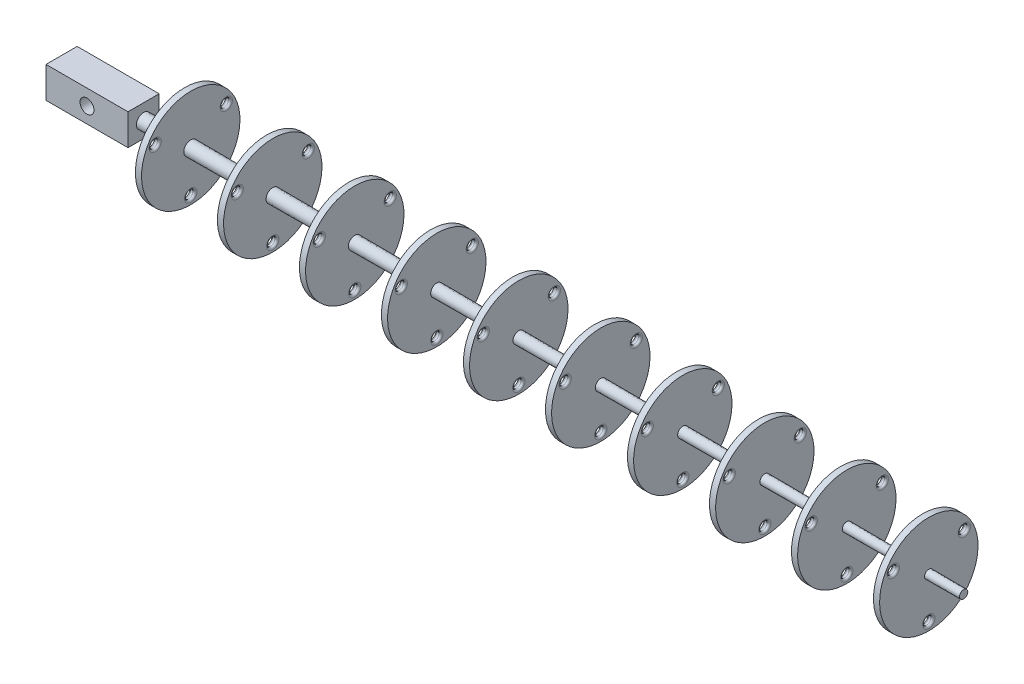
SolidWorks part; units mm, degrees
ref_plane "Front Plane" through (0, 0, 0) normal (0, 0, 1) x (1, 0, 0)
ref_plane "Top Plane" through (0, 0, 0) normal (0, 1, 0) x (1, 0, 0)
ref_plane "Right Plane" through (0, 0, 0) normal (1, 0, 0) x (0, 0, -1)
sketch "Sketch2" plane through (0, 0, 0) normal (0, 0, 1) x (1, 0, 0)
  line L0 (0, 1.75) -> (200, 1)
  line L1 (0, -11) -> (0, 11) construction
  line L2 (200, 1) -> (200, 0)
  line L3 (200, 0) -> (0, 0)
  line L4 (0, 0) -> (0, 1.75)
  dimension "D1" = 1.75
  dimension "D2" = 200
  dimension "D3" = 1
revolve "Revolve1" add sketch "Sketch2" angle 360 about L3
ref_axis "Axis1" through (-3.9062, 0, 0) along (1, 0, 0)
sketch "Sketch3" plane through (0, 0, 0) normal (0, 0, 1) x (1, 0, 0)
  line L0 (10, 0) -> (10, 12)
  line L1 (10, 12) -> (11.5, 12)
  line L2 (11.5, 12) -> (11.5, 0)
  line L3 (11.5, 0) -> (10, 0)
  line L4 (0, -15.4) -> (0, 15.4) construction
  dimension "D1" = 1.5
  dimension "D2" = 12
  dimension "D3" = 10
revolve "Revolve2" add sketch "Sketch3" angle 360 about L3
sketch "Sketch5" plane through (11.5, 0, 0) normal (1, 0, 0) x (0, 0, -1)
  line L0 (0, -10) -> (0, 0) construction
  line L1 (0, 0) -> (8.6603, 5) construction
  line L2 (-8.6603, 5) -> (0, 0) construction
  line L3 (0, 15.4) -> (0, -15.4) construction
  circle A0 centre (0, -10) radius 1
  circle A1 centre (8.6603, 5) radius 1
  circle A2 centre (-8.6603, 5) radius 1
  dimension "D2" = 2
  dimension "D1" = 10
  dimension "D3" = 120
  dimension "D4" = 120
extrude "Cut-Extrude1" cut sketch "Sketch5" against normal up to next
fillet "Fillet1" radius 0.5 6 edges at (10, 4, -8.6603) (10, -11, 0) (11.5, -9, 0) (11.5, 6, -8.6603) (10, 4, 8.6603) (11.5, 6, 8.6603)
pattern_linear "LPattern1" count 10 spacing 20 along (1, 0, 0) of "Revolve2", "Cut-Extrude1", "Fillet1"
sketch "Sketch16" plane through (0, 0, 0) normal (-1, 0, 0) x (0, 0, 1)
  line L1 (-3.8, -3.8) -> (3.8, -3.8)
  line L2 (-3.8, -3.8) -> (-3.8, 3.8)
  line L3 (-3.8, 3.8) -> (3.8, 3.8)
  line L4 (3.8, -3.8) -> (3.8, 3.8)
  line L5 (-3.8, -3.8) -> (3.8, 3.8) construction
  line L6 (-3.8, 3.8) -> (3.8, -3.8) construction
  point P0 (0, 0)
  dimension "D1" = 7.6
extrude "Boss-Extrude1" add sketch "Sketch16" along normal blind 20
sketch "Sketch19" plane through (0, 0, -3.8) normal (0, 0, -1) x (-1, 0, 0)
  line L0 (3.9062, 0) -> (-200, 0) construction
  line L1 (20, 3.8) -> (0, 3.8) construction
  line L2 (20, 3.8) -> (20, -3.8) construction
  point P0 (10, 0)
  point P7 (10, 3.8)
  point P10 (20, 0)
hole_wizard "M3 Clearance Hole1" positions "Sketch19" profile "Sketch18" hole size "M3" standard "ANSI Metric" end condition through all
sketch "Sketch18" plane through (-10, 0, -3.8) normal (1, 0, 0) x (0, 1, 0)
  line L0 (0, 0) -> (0, 15.8)
  line L1 (0, 15.8) -> (1.7, 15.8)
  line L2 (1.7, 15.8) -> (1.7, 0.025)
  line L3 (1.7, 0.025) -> (1.725, 0)
  line L5 (1.725, 0) -> (0, 0)
  line L6 (-1.7, 0.025) -> (-1.725, 0) construction
  line L11 (0, -6.35) -> (0, 107.95) construction
  dimension "Thru Hole Dia." = 3.4
  dimension "Thru Hole Depth" = 15.8
  dimension "Near C'Sink Dia." = 3.45
  dimension "Near C'Sink Angle" = 90
equation "\"R_initial\"= 1.75"
equation "\"D1@Sketch2\"=\"R_initial\""
equation "\"R_distal\"= 1"
equation "\"D3@Sketch2\"=\"R_distal\""
equation "\"L\"=200"
equation "\"D2@Sketch2\"=\"L\""
equation "\"disk_thickness\"= 1.5"
equation "\"D1@Sketch3\"=\"disk_thickness\""
equation "\"disk_radius\"= 12"
equation "\"D2@Sketch3\"=\"disk_radius\""
equation "\"disk_spacing_initial\"= 10"
equation "\"D3@Sketch3\"=\"disk_spacing_initial\""
equation "\"tendon_routing_radius\" = 10"
equation "\"D1@Sketch5\"=\"tendon_routing_radius\""
equation "\"tendon_routing_hole_radius\"=2"
equation "\"D2@Sketch5\"=\"tendon_routing_hole_radius\""
equation "\"tendon_routing_hole_fillet\"=0.5"
equation "\"D1@Fillet1\"=\"tendon_routing_hole_fillet\""
equation "\"inter_disk_spacing\"= 20"
equation "\"D3@LPattern1\"=\"inter_disk_spacing\""
equation "\"num_disk\"= 10"
equation "\"D1@LPattern1\"=\"num_disk\""
